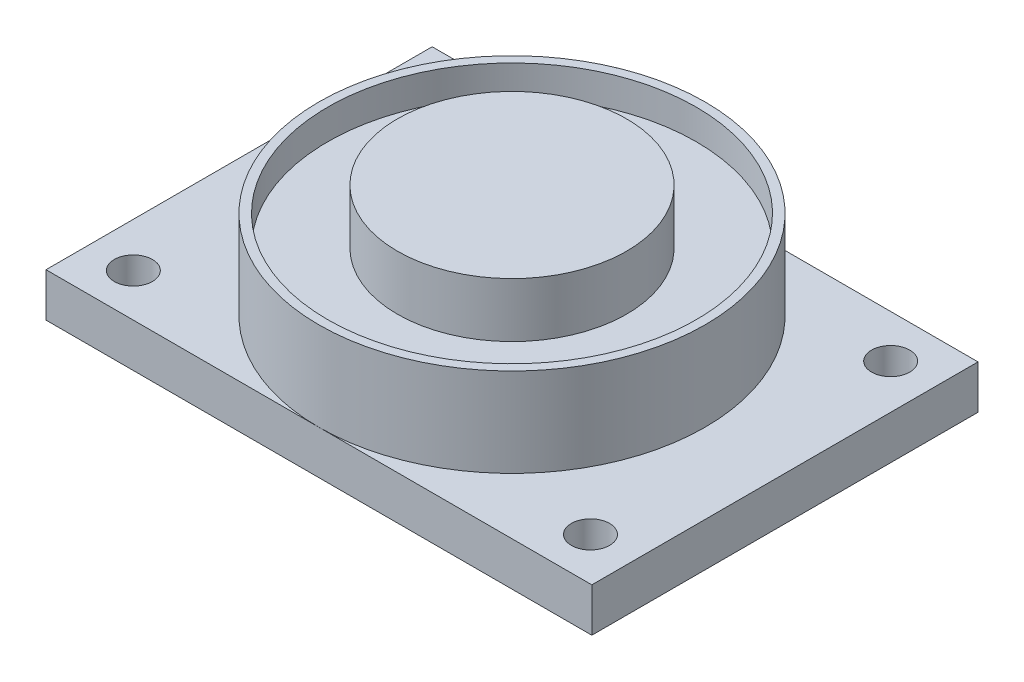
SolidWorks part; units mm, degrees
material "ABS"
ref_plane "Front" through (0, 0, 0) normal (0, 0, 1) x (1, 0, 0)
ref_plane "Top" through (0, 0, 0) normal (0, 1, 0) x (1, 0, 0)
ref_plane "Right" through (0, 0, 0) normal (1, 0, 0) x (0, 0, -1)
sketch "Эскиз1" plane through (0, 0, 0) normal (0, 1, 0) x (1, 0, 0)
  line L1 (20, -14.15) -> (-20, -14.15)
  line L2 (20, -14.15) -> (20, 14.15)
  line L3 (20, 14.15) -> (-20, 14.15)
  line L4 (-20, -14.15) -> (-20, 14.15)
  line L5 (20, -14.15) -> (-20, 14.15) construction
  line L6 (20, 14.15) -> (-20, -14.15) construction
  line L7 (16.75, -11) -> (-16.75, -11)
  line L8 (16.75, -11) -> (16.75, 11)
  line L9 (16.75, 11) -> (-16.75, 11)
  line L10 (-16.75, -11) -> (-16.75, 11)
  line L11 (16.75, -11) -> (-16.75, 11) construction
  line L12 (16.75, 11) -> (-16.75, -11) construction
  circle A0 centre (0, 0) radius 14.15
  circle A1 centre (-16.75, 11) radius 1.4
  circle A2 centre (16.75, 11) radius 1.4
  circle A3 centre (16.75, -11) radius 1.4
  circle A4 centre (-16.75, -11) radius 1.4
  point P0 (0, 0)
  point P6 (0, 0)
  dimension "D5" = 2.8
  dimension "D6" = 2.8
  dimension "D7" = 2.8
  dimension "D8" = 2.8
  dimension "D1" = 22
  dimension "D2" = 33.5
  dimension "D3" = 28.3
  dimension "D4" = 40
extrude "Бобышка-Вытянуть1" add sketch "Эскиз1" against normal blind 3.2 contours L4 L3 L2 L1
extrude "Бобышка-Вытянуть2" add sketch "Эскиз1<3>" along normal blind 6.5 contours A0
sketch "Эскиз1<3>" plane through (0, 0, 0) normal (0, 1, 0) x (1, 0, 0) same geometry as "Эскиз1"
extrude "Вырез-Вытянуть1" cut sketch "Эскиз1<4>" against normal blind 6.5 contours A4 | A3 | A2 | A1
sketch "Эскиз1<4>" plane through (0, 0, 0) normal (0, 1, 0) x (1, 0, 0) same geometry as "Эскиз1"
sketch "Эскиз2" plane through (0, 6.5, 0) normal (0, 1, 0) x (1, 0, 0)
  circle A0 centre (0, 0) radius 8.4
  circle A1 centre (0, 0) radius 13.5
  dimension "D1" = 16.8
  dimension "D2" = 27
extrude "Вырез-Вытянуть2" cut sketch "Эскиз2" against normal blind 2.2
extrude "Бобышка-Вытянуть3" add sketch "Эскиз2<2>" along normal blind 4 from offset 2.2 contours A0 region at (0, 6.5, 0) offset against normal yes
sketch "Эскиз2<2>" plane through (0, 6.5, 0) normal (0, 1, 0) x (1, 0, 0) same geometry as "Эскиз2"
sketch "Эскиз4" plane through (0, -3.2, 0) normal (0, -1, 0) x (1, 0, 0)
  line L0 (5.925, 0) -> (-5.925, 0) construction
  line L1 (5.925, -13.325) -> (-5.925, -13.325)
  line L2 (5.925, 13.325) -> (-5.925, 13.325)
  line L3 (5.925, -11.325) -> (-5.925, -11.325)
  line L4 (5.925, 11.325) -> (-5.925, 11.325)
  line L5 (5.925, -7.825) -> (-5.925, -7.825)
  line L6 (5.925, 7.825) -> (-5.925, 7.825)
  circle A0 centre (0, 0) radius 7.5
  circle A1 centre (0, 0) radius 5.9
  arc A2 (5.925, -13.325) -> (5.925, 13.325) centre (5.925, 0) ccw
  arc A3 (-5.925, 13.325) -> (-5.925, -13.325) centre (-5.925, 0) ccw
  arc A4 (-5.925, 11.325) -> (-5.925, -11.325) centre (-5.925, 0) ccw
  arc A5 (5.925, -11.325) -> (5.925, 11.325) centre (5.925, 0) ccw
  arc A6 (-5.925, 7.825) -> (-5.925, -7.825) centre (-5.925, 0) ccw
  arc A7 (5.925, -7.825) -> (5.925, 7.825) centre (5.925, 0) ccw
  point P6 (0, 0)
  dimension "D1" = 26.65
  dimension "D5" = 11.8
  dimension "D6" = 15
  dimension "D2" = 11.85
  dimension "D3" = 2
  dimension "D4" = 3.5
extrude "Вырез-Вытянуть3" cut sketch "Эскиз4" against normal blind 0.2 contours A3 L1 A2 L2
extrude "Вырез-Вытянуть4" cut sketch "Эскиз4<3>" against normal blind 1 contours L3 A5 L4 A4 A7 L5 A6 L6 | L5 A7 L6 A6 A0 | A0 A1 | A1 L0 | L0 A1 region at (0, -3.2, -2.504) region at (0, -3.2, 2.504) region at (0, -3.2, -10.9123) region at (0, -3.2, -7.5086) region at (-7.2879, -3.2, 0)
sketch "Эскиз4<3>" plane through (0, -3.2, 0) normal (0, -1, 0) x (1, 0, 0) same geometry as "Эскиз4"
extrude "Бобышка-Вытянуть5" add sketch "Эскиз4<12>" against normal blind 1 contours A6 L5 A7 L6
sketch "Эскиз4<12>" plane through (0, -3.2, 0) normal (0, -1, 0) x (1, 0, 0) same geometry as "Эскиз4"
extrude "Вырез-Вытянуть7" cut sketch "Эскиз4<13>" against normal blind 1 draft 60 contours A6 L5 A7 L6
sketch "Эскиз4<13>" plane through (0, -3.2, 0) normal (0, -1, 0) x (1, 0, 0) same geometry as "Эскиз4"
extrude "Бобышка-Вытянуть6" add sketch "Эскиз4<14>" against normal blind 1 contours A0
sketch "Эскиз4<14>" plane through (0, -3.2, 0) normal (0, -1, 0) x (1, 0, 0) same geometry as "Эскиз4"
extrude "Вырез-Вытянуть8" cut sketch "Эскиз4<15>" against normal blind 1 draft 60 contours A0
sketch "Эскиз4<15>" plane through (0, -3.2, 0) normal (0, -1, 0) x (1, 0, 0) same geometry as "Эскиз4"
extrude "Бобышка-Вытянуть7" add sketch "Эскиз4<16>" against normal blind 1 contours A1
sketch "Эскиз4<16>" plane through (0, -3.2, 0) normal (0, -1, 0) x (1, 0, 0) same geometry as "Эскиз4"
fillet "Скругление2" radius 10 1 edges at (0, -3.2, -5.9)
fillet "Скругление3" radius 1 8 edges at (0, -2.2, 7.825) (13.75, -2.2, 0) (0, -2.2, -7.825) (0, -2.2, 11.325) (17.25, -2.2, 0) (0, -2.2, -11.325) (-13.75, -2.2, 0) (-17.25, -2.2, 0)
fillet "Скругление4" radius 0.2 9 edges at (0, -3.2, 7.825) (13.75, -3.2, 0) (0, -3.2, -7.825) (0, -3.2, -7.5) (-13.75, -3.2, 0) (0, -3, 11.325) (17.25, -3, 0) (0, -3, -11.325) (-17.25, -3, 0)
fillet "Скругление5" radius 2 6 edges at (5.1492, -2.2, -6.0929) (5.1492, -2.2, 6.0929) (-5.1492, -2.2, 6.0929) (-5.1492, -2.2, -6.0929) (12.0179, -2.2, 0) (-12.0179, -2.2, 0)
